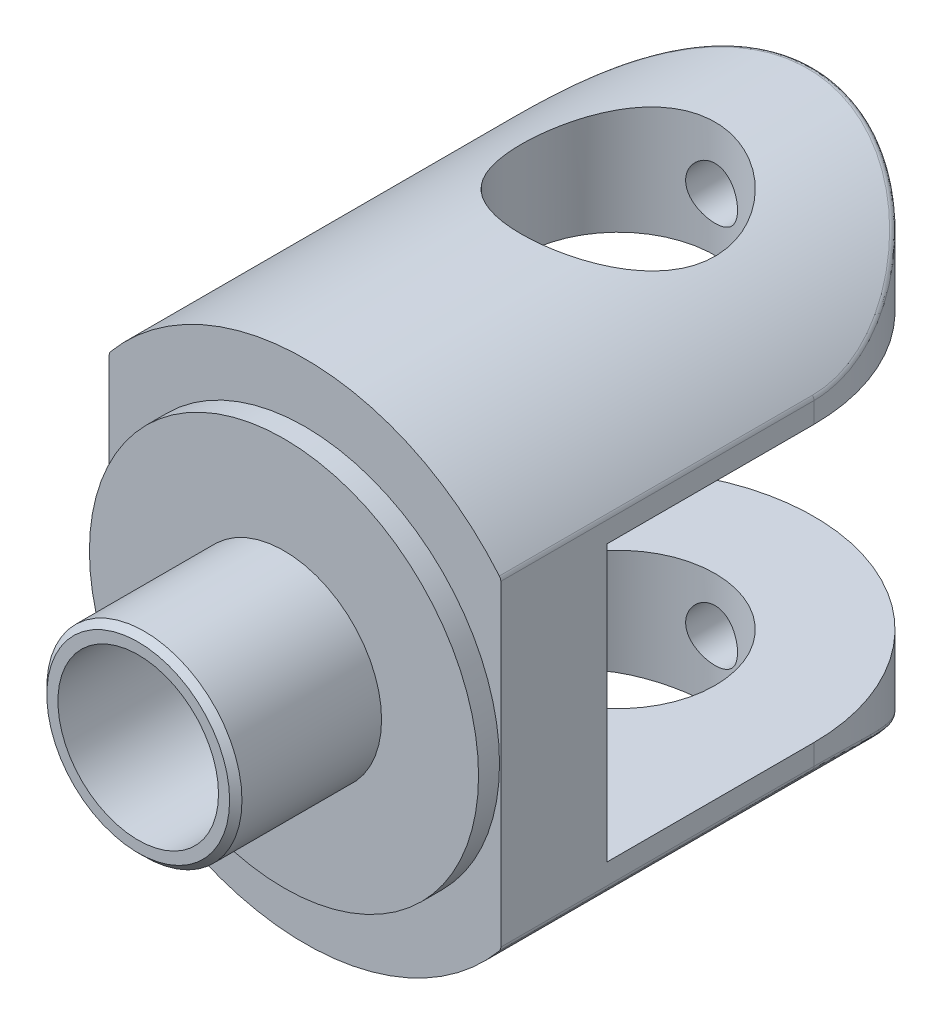
SolidWorks part; units mm, degrees
ref_plane "Front Plane" through (0, 0, 0) normal (0, 0, 1) x (1, 0, 0)
ref_plane "Top Plane" through (0, 0, 0) normal (0, 1, 0) x (1, 0, 0)
ref_plane "Right Plane" through (0, 0, 0) normal (1, 0, 0) x (0, 0, -1)
sketch "Sketch1" plane through (0, 0, 0) normal (0, 0, 1) x (1, 0, 0)
  circle A0 centre (0, 0) radius 15.75
  dimension "D1" = 31.5
extrude "Boss-Extrude1" add sketch "Sketch1" along normal blind 1.7
sketch "Sketch2" plane through (0, 0, 1.7) normal (0, 0, 1) x (1, 0, 0)
  circle A0 centre (0, 0) radius 7.9
  dimension "D1" = 15.8
extrude "Boss-Extrude2" add sketch "Sketch2" along normal blind 11.8
sketch "Sketch3" plane through (0, 0, 0) normal (0, 0, -1) x (-1, 0, 0)
  circle A0 centre (0, 0) radius 20.5
  dimension "D1" = 41
extrude "Boss-Extrude3" add sketch "Sketch3" along normal blind 41.2
sketch "Sketch4" plane through (0, 0, -41.2) normal (0, 0, -1) x (-1, 0, 0)
  line L0 (0, 24.8109) -> (0, -28.0062) construction
  line L1 (-15.85, 13.0011) -> (-15.85, -13.0011)
  line L2 (15.85, 13.0011) -> (15.85, -13.0011)
  line L4 (-15.85, 24.8109) -> (-15.85, -28.0062) construction
  line L5 (15.85, 24.8109) -> (15.85, -28.0062) construction
  circle A0 centre (0, 0) radius 20.5 construction
  arc A1 (-15.85, 13.0011) -> (-15.85, -13.0011) centre (0, 0) ccw
  arc A2 (15.85, -13.0011) -> (15.85, 13.0011) centre (0, 0) ccw
  dimension "D1" = 15.85
  dimension "D2" = 15.85
extrude "Cut-Extrude1" cut sketch "Sketch4" against normal up to surface (41.2 mm away) up to face at (15.75, 0, 0)
ref_plane "Plane1" through (0, 0, 0) normal (0, 1, 0) x (1, 0, 0)
sketch "Sketch5" plane through (0, 0, 0) normal (0, 1, 0) x (1, 0, 0)
  line L0 (0, -13.5) -> (0, 45.2177) construction
  line L1 (-7.9, -13.5) -> (7.9, -13.5) construction
  line L2 (15.85, 41.2) -> (-15.85, 41.2) construction
  line L3 (15.85, 0) -> (15.85, 41.2) construction
  line L4 (-15.85, 0) -> (-15.85, 41.2) construction
  line L5 (15.85, 25.35) -> (15.85, 41.2)
  line L6 (15.85, 41.2) -> (-15.85, 41.2)
  line L7 (-15.85, 25.35) -> (-15.85, 41.2)
  arc A0 (15.85, 25.35) -> (-15.85, 25.35) centre (0, 25.35) ccw
  dimension "D1" = 15.85
  dimension "31,7" = 31.7
extrude "Cut-Extrude2" cut sketch "Sketch5" against normal mid plane 41.2 contours A0 L5 L6 | A0 L6 L7 region at (12.3096, 0, -37.6596) region at (-12.3096, 0, -37.6596)
sketch "Sketch6" plane through (-15.85, 0, 0) normal (-1, 0, 0) x (0, 0, 1)
  line L0 (-41.2, 20.5) -> (-41.2, -20.5) construction
  line L1 (-41.2, 11.15) -> (-8.6, 11.15)
  line L2 (-41.2, 11.15) -> (-41.2, -11.15)
  line L3 (-41.2, -11.15) -> (-8.6, -11.15)
  line L4 (-8.6, 11.15) -> (-8.6, -11.15)
  line L5 (17.435, 0) -> (-17.435, 0) construction
  line L6 (1.7, -15.75) -> (1.7, 15.75) construction
  dimension "D1" = 22.3
  dimension "D2" = 11.15
  dimension "D3" = 10.3
extrude "Cut-Extrude3" cut sketch "Sketch6" against normal up to surface (31.7 mm away) up to face at (15.85, 0, -12.675)
sketch "Sketch7" plane through (0, 0, 0) normal (0, 1, 0) x (1, 0, 0)
  circle A0 centre (0, 25.35) radius 7.85
  dimension "D1" = 15.7
extrude "Cut-Extrude4" cut sketch "Sketch7" against normal mid plane 41.2
sketch "Sketch9" plane through (0, 0, 13.5) normal (0, 0, 1) x (1, 0, 0)
  circle A0 centre (0, 0) radius 6.5
  dimension "D1" = 13
extrude "Cut-Extrude5" cut sketch "Sketch9" against normal up to surface (22.1 mm away) up to face at (0, 0, -8.6)
chamfer "Chamfer1" distance 0.5 angle 45 1 edges at (7.9, 0, 13.5)
fillet "Fillet1" radius 0.5 6 edges at (-15.85, -13.0011, -12.675) (0, -20.5, -41.2) (-15.85, 13.0011, -12.675) (0, 20.5, -41.2) (15.85, -13.0011, -12.675) (15.85, 13.0011, -12.675)
sketch "Sketch10" plane through (-15.85, 0, 0) normal (-1, 0, 0) x (0, 0, 1)
  line L0 (18.3077, 0) -> (-18.3077, 0) construction
  line L1 (0, -12.821) -> (0, 12.821) construction
  circle A0 centre (-4, 0) radius 2.5
  dimension "D1" = 5
  dimension "D2" = 4
extrude "Cut-Extrude6" cut sketch "Sketch10" against normal up to surface (9.35 mm away) up to face at (0, -6.5, -8.6)
thread "Thread1" pitch 1 method extrude profile "Thread Profile1" start angle 0, offset 0, length 10, pitch 1, diameter 5
ref_plane "Plane2" through (-15.85, 0, -6.5) normal (0, -1, 0) x (0, 0, -1)
sketch "Thread Profile1" plane through (-15.85, 0, -6.5) normal (0, -1, 0) x (0, 0, -1)
  line L0 (0, 0) -> (0, 1) construction
  line L11 (0, 0) -> (0, 0.875)
  line L12 (0, 0.875) -> (-0.5413, 0.5625)
  line L13 (-0.5413, 0.5625) -> (-0.5413, 0.3125)
  line L15 (-0.5413, 0.3125) -> (0, 0)
  line L17 (-0.5413, 0.4375) -> (0, 0.4375) construction
  point P2 (0, 0)
  dimension "Pitch" = 1
  dimension "Profile_Angle" = 60
  dimension "Profile_Land" = 0.25
  dimension "Profile_Height" = 0.5413
sketch "Sketch13" plane through (0, 0, 13.5) normal (0, 0, 1) x (1, 0, 0)
  circle A0 centre (0, 0) radius 6.5
  dimension "D1" = 13
extrude "Cut-Extrude7" cut sketch "Sketch13" against normal blind 40.8
ref_plane "Plane3" through (0, 0, -40.6) normal (0, 0, -1) x (-1, 0, 0)
sketch "Sketch14" plane through (0, 0, -40.6) normal (0, 0, -1) x (-1, 0, 0)
  line L0 (18.3077, 0) -> (-18.3077, 0) construction
  line L1 (15.85, -11.15) -> (15.85, 11.15) construction
  circle A0 centre (0, 15.5) radius 2.1
  circle A1 centre (0, -15.5) radius 2.1
  dimension "D1" = 4.2
  dimension "D2" = 4.2
  dimension "D5" = 15.85
  dimension "D6" = 15.85
  dimension "D3" = 15.5
  dimension "D4" = 15.5
extrude "Cut-Extrude8" cut sketch "Sketch14" against normal mid plane 30
cosmetic thread "Cosmetic Thread1" parameters "D2"=5
cosmetic thread "Cosmetic Thread2" parameters "D2"=5
